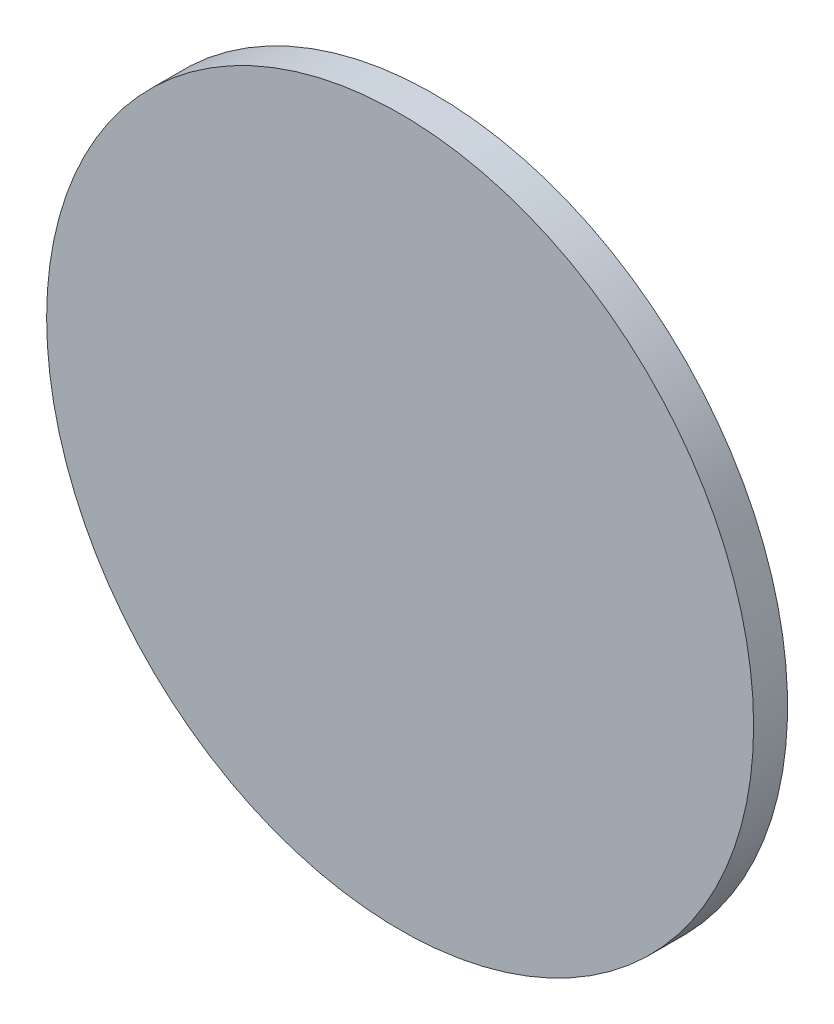
SolidWorks part; units mm, degrees
ref_plane "Front Plane" through (0, 0, 0) normal (0, 0, 1) x (1, 0, 0)
ref_plane "Top Plane" through (0, 0, 0) normal (0, 1, 0) x (1, 0, 0)
ref_plane "Right Plane" through (0, 0, 0) normal (1, 0, 0) x (0, 0, -1)
sketch "Sketch1" plane through (0, 0, 0) normal (0, 1, 0) x (1, 0, 0)
  line L0 (0, 0) -> (0, -38.7874) construction
  line L1 (0, 0) -> (52.047, 0)
  line L2 (52.047, 0) -> (52.047, -10)
  line L3 (52.047, -10) -> (0, -10)
  line L4 (0, -10) -> (0, 0)
  dimension "D1" = 52.047
  dimension "D2" = 10
revolve "Revolve1" add sketch "Sketch1" angle 360 about L0
sketch "Sketch2" plane through (0, 0, 0) normal (0, 0, -1) x (-1, 0, 0)
  circle A0 centre (0, 0) radius 6
extrude "Boss-Extrude1" add sketch "Sketch2" along normal blind 15 and the other way blind 5
chamfer "Chamfer1" distance 0.5 angle 45 1 edges at (-6, 0, -15)
thread "Thread1" pitch 1.5 method cut profile "Thread Profile1" start angle 0, offset 2, length 0, pitch 1.5, diameter 12
ref_plane "Plane1" through (-6, 0, -2) normal (0, -1, 0) x (-1, 0, 0)
sketch "Thread Profile1" plane through (-6, 0, -2) normal (0, -1, 0) x (-1, 0, 0)
  line L0 (0, 0) -> (0, 1.5) construction
  line L11 (0, 0) -> (0, 1.3125)
  line L12 (0, 1.3125) -> (-0.8119, 0.8437)
  line L13 (-0.8119, 0.8437) -> (-0.8119, 0.4687)
  line L15 (-0.8119, 0.4687) -> (0, 0)
  line L17 (-0.8119, 0.6562) -> (0, 0.6562) construction
  point P2 (0, 0)
  dimension "Pitch" = 1.5
  dimension "Profile_Angle" = 60
  dimension "Profile_Land" = 0.375
  dimension "Profile_Height" = 0.8119
fillet "Fillet1" radius 0.5 1 edges at (6, 0, 0)
sketch "Sketch3" plane through (0, 0, 10) normal (0, 0, 1) x (1, 0, 0)
  circle A0 centre (0, 0) radius 52.047
extrude "Cut-Extrude1" cut sketch "Sketch3" against normal blind 5
